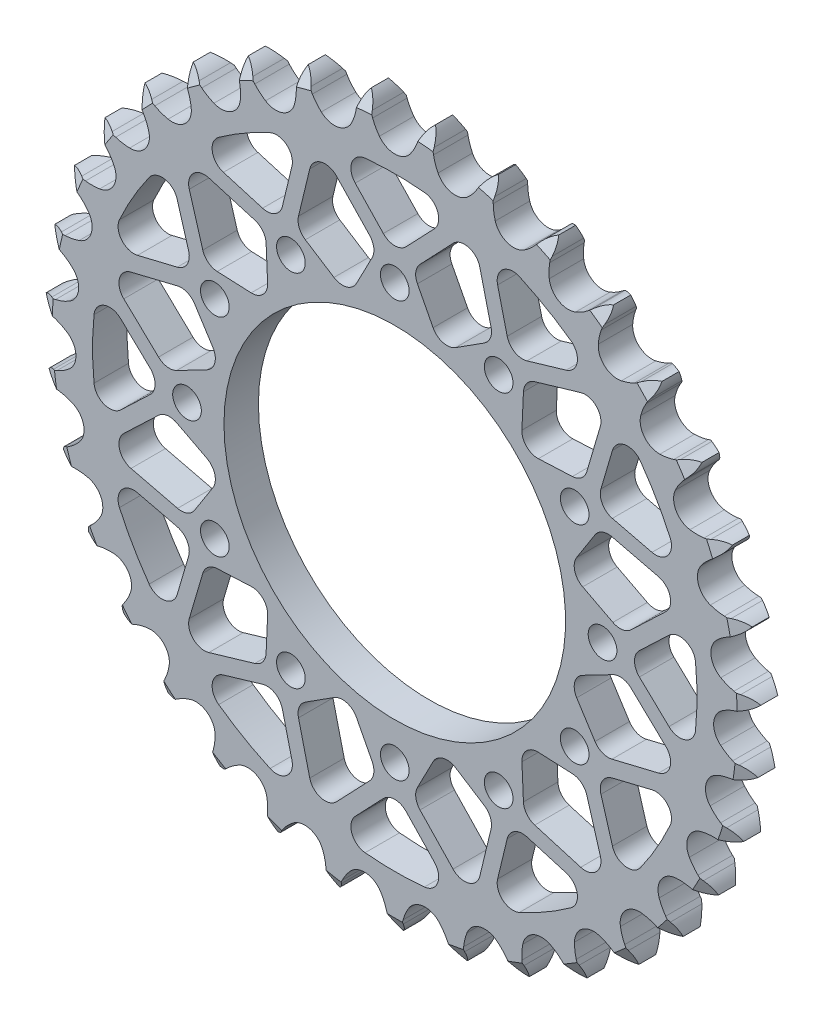
SolidWorks part; units mm, degrees
material "7075-T6 (SN)"
ref_plane "Front Plane" through (0, 0, 0) normal (0, 0, 1) x (1, 0, 0)
ref_plane "Top Plane" through (0, 0, 0) normal (0, 1, 0) x (1, 0, 0)
ref_plane "Right Plane" through (0, 0, 0) normal (1, 0, 0) x (0, 0, -1)
sketch "Work Sketch" plane through (0, 0, 0) normal (0, 0, 1) x (1, 0, 0)
  line L0 (0, 0) -> (0, 160.4542) construction
  line L1 (-112.0919, 70.8395) -> (87.2579, 70.8395) construction
  line L2 (5.0903, 120.8822) -> (5.0903, 112.9699) construction
  line L3 (-12.8497, 74.6356) -> (16.7256, 74.6356) construction
  line L4 (5.0903, 74.6356) -> (-6.074, 66.3097) construction
  line L5 (5.0903, 74.6356) -> (-4.641, 71.0332) construction
  line L6 (-4.641, 71.0332) -> (-6.9559, 77.2865)
  line L7 (-11.5114, 69.8433) -> (-7.1525, 69.8433) construction
  line L8 (-11.0678, 124.7602) -> (-11.0678, 110.2345) construction
  line L9 (0, 0) -> (-3.8324, 42.5811) construction
  circle A0 centre (0, 0) radius 70.8395
  circle A1 centre (0, 70.8395) radius 4.0088
  arc A2 (-4.641, 71.0332) -> (-3.2136, 68.4429) centre (5.0682, 74.6949) ccw
  circle A3 centre (-11.0678, 69.8433) radius 6.4401
  point P23 (-3.2136, 68.4429)
  dimension "D1" = 141.6789
  dimension "D8" = 10.3767
  dimension "D2" = 8.0177
  dimension "D3" = 5.0903
  dimension "D4" = 3.7962
  dimension "D5" = 36.714
  dimension "D6" = 16.4
  dimension "D7" = 10.3767
  dimension "D9" = 0.9961
  dimension "D10" = 11.0678
  dimension "D11" = 5.143
sketch "Teeth Sketch" plane through (0, 0, 0) normal (0, 0, 1) x (1, 0, 0)
  line L0 (5.0282, 72.0792) -> (4.641, 71.0332)
  line L1 (-8.3399, 92.6643) -> (-5.3292, 59.2127) construction
  line L2 (0, 0) -> (-12.1309, 132.2) construction
  line L3 (7.9229, 71.8186) -> (8.1171, 70.7203)
  line L4 (17927.8618, -199194.8588) -> (-17931.6941, 199237.4399) construction
  line L5 (0, 146.3285) -> (0, 56.9858) construction
  line L6 (17.8176, 70.023) -> (17.2498, 69.063)
  line L7 (0, -200000) -> (0, 200160.4542) construction
  line L8 (20.6192, 69.2498) -> (20.6142, 68.1345)
  line L9 (-4.641, 71.0332) -> (-6.9559, 77.2865) construction
  line L10 (43.6371, 57.589) -> (43.2405, 56.5465)
  line L11 (-5.0282, 72.0792) -> (-4.641, 71.0332)
  line L12 (30.0344, 65.7163) -> (29.3043, 64.873)
  line L13 (32.6529, 64.4552) -> (32.4488, 63.3587)
  line L14 (41.2858, 59.2973) -> (40.4169, 58.598)
  line L15 (51.2103, 50.9725) -> (50.2305, 50.4396)
  line L16 (53.2187, 48.8718) -> (52.6424, 47.9169)
  line L17 (59.4888, 41.0094) -> (58.4296, 40.66)
  line L18 (61.0899, 38.5838) -> (60.3523, 37.7472)
  line L19 (65.8553, 29.7283) -> (64.7507, 29.5736)
  line L20 (66.9976, 27.0558) -> (66.1224, 26.3643)
  line L21 (70.1052, 17.4916) -> (68.9907, 17.5366)
  line L22 (70.7519, 14.6581) -> (69.7673, 14.134)
  line L23 (72.1018, 4.6927) -> (71.0133, 4.9361)
  line L24 (72.2322, 1.7893) -> (71.1699, 1.4494)
  line L25 (71.781, -8.2569) -> (70.7534, -7.8232)
  line L26 (71.3909, -11.137) -> (70.2849, -11.2818)
  line L27 (69.1531, -20.9412) -> (68.2195, -20.331)
  line L28 (68.255, -23.7054) -> (67.141, -23.6503)
  line L29 (64.3026, -32.9525) -> (63.493, -32.1853)
  line L30 (62.9254, -35.5118) -> (61.8391, -35.2587)
  line L31 (57.3853, -43.9046) -> (56.7257, -43.0052)
  line L32 (55.5732, -46.1769) -> (54.5496, -45.7339)
  line L33 (48.6237, -53.4456) -> (48.1352, -52.4428)
  line L34 (46.435, -55.3578) -> (45.5069, -54.7392)
  line L35 (38.2992, -61.2688) -> (37.9976, -60.1949)
  line L36 (35.8042, -62.7594) -> (35.0015, -61.985)
  line L37 (26.7437, -67.1227) -> (26.6388, -66.0123)
  line L38 (24.0227, -68.144) -> (23.3712, -67.2387)
  line L39 (14.3287, -70.8193) -> (14.4237, -69.708)
  line L40 (11.4691, -71.3383) -> (10.9896, -70.3312)
  line L41 (1.4532, -72.2397) -> (1.7451, -71.1632)
  line L42 (-1.4532, -72.2397) -> (-1.7451, -71.1632)
  line L43 (-11.4691, -71.3383) -> (-10.9896, -70.3312)
  line L44 (-14.3287, -70.8193) -> (-14.4237, -69.708)
  line L45 (-24.0227, -68.144) -> (-23.3712, -67.2387)
  line L46 (-26.7437, -67.1227) -> (-26.6388, -66.0123)
  line L47 (-35.8042, -62.7594) -> (-35.0015, -61.985)
  line L48 (-38.2992, -61.2688) -> (-37.9976, -60.1949)
  line L49 (-46.435, -55.3578) -> (-45.5069, -54.7392)
  line L50 (-48.6237, -53.4456) -> (-48.1352, -52.4428)
  line L51 (-55.5732, -46.1769) -> (-54.5496, -45.7339)
  line L52 (-57.3853, -43.9046) -> (-56.7257, -43.0052)
  line L53 (-62.9254, -35.5118) -> (-61.8391, -35.2587)
  line L54 (-64.3026, -32.9525) -> (-63.493, -32.1853)
  line L55 (-68.255, -23.7054) -> (-67.141, -23.6503)
  line L56 (-69.1531, -20.9412) -> (-68.2195, -20.331)
  line L57 (-71.3909, -11.137) -> (-70.2849, -11.2818)
  line L58 (-71.781, -8.2569) -> (-70.7534, -7.8232)
  line L59 (-72.2322, 1.7893) -> (-71.1699, 1.4494)
  line L60 (-72.1018, 4.6927) -> (-71.0133, 4.9361)
  line L61 (-70.7519, 14.6581) -> (-69.7673, 14.134)
  line L62 (-70.1052, 17.4916) -> (-68.9907, 17.5366)
  line L63 (-66.9976, 27.0558) -> (-66.1224, 26.3643)
  line L64 (-65.8553, 29.7283) -> (-64.7507, 29.5736)
  line L65 (-61.0899, 38.5838) -> (-60.3523, 37.7472)
  line L66 (-59.4888, 41.0094) -> (-58.4296, 40.66)
  line L67 (-53.2187, 48.8718) -> (-52.6424, 47.9169)
  line L68 (-51.2103, 50.9725) -> (-50.2305, 50.4396)
  line L69 (-43.6371, 57.589) -> (-43.2405, 56.5465)
  line L70 (-41.2858, 59.2973) -> (-40.4169, 58.598)
  line L71 (-32.6529, 64.4552) -> (-32.4488, 63.3587)
  line L72 (-30.0344, 65.7163) -> (-29.3043, 64.873)
  line L73 (-20.6192, 69.2498) -> (-20.6142, 68.1345)
  line L74 (-17.8176, 70.023) -> (-17.2498, 69.063)
  line L75 (-7.9229, 71.8186) -> (-8.1171, 70.7203)
  arc A0 (-6.856, 74.7153) -> (-5.0282, 72.0792) centre (-11.0678, 69.8433) cw
  circle A1 centre (-11.0678, 69.8433) radius 6.4401 construction
  arc A2 (-3.2136, 68.4429) -> (-4.641, 71.0332) centre (5.0682, 74.6949) cw
  arc A3 (-4.641, 71.0332) -> (-3.2136, 68.4429) centre (5.0682, 74.6949) ccw construction
  circle A4 centre (0, 70.8395) radius 4.0088 construction
  arc A5 (-3.2136, 68.4429) -> (3.2136, 68.4429) centre (0, 70.8395) ccw
  arc A6 (3.2136, 68.4429) -> (4.641, 71.0332) centre (-5.0682, 74.6949) ccw
  arc A7 (6.856, 74.7153) -> (5.0282, 72.0792) centre (11.0678, 69.8433) ccw
  arc A8 (6.5951, 74.7388) -> (7.9229, 71.8186) centre (1.5811, 70.6972) cw
  arc A9 (9.059, 67.9168) -> (8.1171, 70.7203) centre (18.324, 72.5896) cw
  arc A10 (9.059, 67.9168) -> (15.3829, 66.7692) centre (12.6489, 69.701) ccw
  arc A11 (15.3829, 66.7692) -> (17.2498, 69.063) centre (8.3506, 74.3995) ccw
  arc A12 (20.0867, 72.2905) -> (17.8176, 70.023) centre (23.3609, 66.7447) ccw
  arc A13 (19.8343, 72.3601) -> (20.6192, 69.2498) centre (14.1792, 69.2787) cw
  arc A14 (21.0404, 65.2078) -> (20.6142, 68.1345) centre (30.9909, 68.1512) cw
  arc A15 (21.0404, 65.2078) -> (27.0578, 62.9494) centre (24.8912, 66.3224) ccw
  arc A16 (27.0578, 62.9494) -> (29.3043, 64.873) centre (21.5009, 71.7128) ccw
  arc A17 (32.6719, 67.5421) -> (30.0344, 65.7163) centre (34.9032, 61.5008) ccw
  arc A18 (32.4359, 67.6557) -> (32.6529, 64.4552) centre (26.3215, 65.6336) cw
  arc A19 (32.3456, 60.403) -> (32.4488, 63.3587) centre (42.6617, 61.5223) cw
  arc A20 (32.3456, 60.403) -> (37.863, 57.1065) centre (36.3335, 60.812) ccw
  arc A21 (37.863, 57.1065) -> (40.4169, 58.598) centre (33.9602, 66.7212) ccw
  arc A22 (44.207, 60.6229) -> (41.2858, 59.2973) centre (45.3237, 54.2803) ccw
  arc A23 (43.9951, 60.7768) -> (43.6371, 57.589) centre (37.6178, 59.8789) cw
  arc A24 (42.6112, 53.6567) -> (43.2405, 56.5465) centre (52.9614, 52.9161) cw
  arc A25 (42.6112, 53.6567) -> (47.4513, 49.428) centre (46.608, 53.3472) ccw
  arc A26 (47.4513, 49.428) -> (50.2305, 50.4396) centre (45.328, 59.5852) ccw
  arc A27 (54.3212, 51.7552) -> (51.2103, 50.9725) centre (54.2875, 45.3151) ccw
  arc A28 (54.1402, 51.9445) -> (53.2187, 48.8718) centre (47.7051, 52.1997) cw
  arc A29 (51.5072, 45.1859) -> (52.6424, 47.9169) centre (61.5588, 42.6091) cw
  arc A30 (51.5072, 45.1859) -> (55.5144, 40.161) centre (55.3845, 44.1677) ccw
  arc A31 (55.5144, 40.161) -> (58.4296, 40.66) centre (55.2389, 50.534) ccw
  arc A32 (62.6894, 41.224) -> (59.4888, 41.0094) centre (61.5064, 34.8935) ccw
  arc A33 (62.5452, 41.4426) -> (61.0899, 38.5838) centre (56.2591, 42.8428) cw
  arc A34 (58.7477, 35.2628) -> (60.3523, 37.7472) centre (68.1777, 30.9326) cw
  arc A35 (58.7477, 35.2628) -> (61.7933, 29.6031) centre (62.3809, 33.5686) ccw
  arc A36 (61.7933, 29.6031) -> (64.7507, 29.5736) centre (63.3744, 39.8586) ccw
  arc A37 (69.0428, 29.3679) -> (65.8553, 29.7283) centre (66.7484, 23.3503) ccw
  arc A38 (68.9399, 29.6087) -> (66.9976, 27.0558) centre (63.0048, 32.1088) cw
  arc A39 (64.1, 24.2063) -> (66.1224, 26.3643) centre (72.6052, 18.2619) cw
  arc A40 (64.1, 24.2063) -> (66.0861, 18.0937) centre (67.3723, 21.8906) ccw
  arc A41 (66.0861, 18.0937) -> (68.9907, 17.5366) centre (69.4729, 27.9021) ccw
  arc A42 (73.1771, 16.5679) -> (70.1052, 17.4916) centre (69.8451, 11.0567) ccw
  arc A43 (73.1188, 16.8232) -> (70.7519, 14.6581) centre (67.7256, 20.3429) cw
  arc A44 (67.3921, 12.3718) -> (69.7673, 14.134) centre (74.6992, 5.0042) cw
  arc A45 (67.3921, 12.3718) -> (68.2548, 6.0028) centre (70.1983, 9.509) ccw
  arc A46 (68.2548, 6.0028) -> (71.0133, 4.9361) centre (73.3386, 15.0489) ccw
  arc A47 (74.9595, 3.2354) -> (72.1018, 4.6927) centre (70.6969, -1.5923) ccw
  arc A48 (74.9477, 3.497) -> (72.2322, 1.7893) centre (70.2696, 7.9231) cw
  arc A49 (68.5181, 0.1397) -> (71.1699, 1.4494) centre (74.3923, -8.4143) cw
  arc A50 (68.5181, 0.1397) -> (68.2298, -6.281) centre (70.7681, -3.1782) ccw
  arc A51 (68.2298, -6.281) -> (70.7534, -7.8232) centre (74.8471, 1.7119) ccw
  arc A52 (74.3325, -10.2012) -> (71.781, -8.2569) centre (69.2765, -14.1901) ccw
  arc A53 (74.3677, -9.9416) -> (71.3909, -11.137) centre (70.555, -4.7513) cw
  arc A54 (67.442, -12.097) -> (70.2849, -11.2818) centre (71.6944, -21.5623) cw
  arc A55 (67.442, -12.097) -> (66.0118, -18.363) centre (69.0634, -15.7633) ccw
  arc A56 (66.0118, -18.363) -> (68.2195, -20.331) centre (73.9499, -11.6801) ccw
  arc A57 (71.3165, -23.3098) -> (69.1531, -20.9412) centre (65.6294, -26.3319) ccw
  arc A58 (71.3974, -23.0607) -> (68.255, -23.7054) centre (68.5728, -17.2731) cw
  arc A59 (64.1981, -23.9448) -> (67.141, -23.6503) centre (66.6921, -34.0173) cw
  arc A60 (64.1981, -23.9448) -> (61.6721, -29.8547) centre (65.1388, -27.8417) ccw
  arc A61 (61.6721, -29.8547) -> (63.493, -32.1853) centre (70.676, -24.6966) ccw
  arc A62 (66.0083, -35.6693) -> (64.3026, -32.9525) centre (59.873, -37.6273) ccw
  arc A63 (66.1324, -35.4386) -> (62.9254, -35.5118) centre (64.3866, -29.2396) cw
  arc A64 (58.8909, -35.023) -> (61.8391, -35.2587) centre (59.5463, -45.379) cw
  arc A65 (58.8909, -35.023) -> (55.3502, -40.3869) centre (59.1207, -39.0252) ccw
  arc A66 (55.3502, -40.3869) -> (56.7257, -43.0052) centre (65.1304, -36.9194) ccw
  arc A67 (58.5785, -46.8823) -> (57.3853, -43.9046) centre (52.1922, -47.7133) ccw
  arc A68 (58.7418, -46.6775) -> (55.5732, -46.1769) centre (58.1309, -40.2664) cw
  arc A69 (51.6909, -44.9755) -> (54.5496, -45.7339) centre (50.4867, -55.2821) cw
  arc A70 (51.6909, -44.9755) -> (47.2494, -49.6211) centre (51.2024, -48.9545) ccw
  arc A71 (47.2494, -49.6211) -> (48.1352, -52.4428) centre (57.4915, -47.9556) ccw
  arc A72 (49.266, -56.5885) -> (48.6237, -53.4456) centre (42.8339, -56.2658) ccw
  arc A73 (49.4632, -56.4161) -> (46.435, -55.3578) centre (50.0069, -49.999) cw
  arc A74 (42.8296, -53.4825) -> (45.5069, -54.7392) centre (39.8043, -63.4085) cw
  arc A75 (42.8296, -53.4825) -> (37.6299, -57.2603) centre (41.6384, -57.3103) ccw
  arc A76 (37.6299, -57.2603) -> (37.9976, -60.1949) centre (48.0048, -57.4505) ccw
  arc A77 (38.37, -64.4758) -> (38.2992, -61.2688) centre (32.0989, -63.0099) ccw
  arc A78 (38.5948, -64.3415) -> (35.8042, -62.7594) centre (40.2756, -58.1246) cw
  arc A79 (32.5916, -60.2706) -> (35.0015, -61.985) centre (27.8426, -69.4968) cw
  arc A80 (32.5916, -60.2706) -> (26.8009, -63.0592) centre (30.7361, -63.8241) ccw
  arc A81 (26.8009, -63.0592) -> (26.6388, -66.0123) centre (36.9752, -65.0988) ccw
  arc A82 (26.2407, -70.2909) -> (26.7437, -67.1227) centre (20.3322, -67.7288) ccw
  arc A83 (26.4859, -70.1989) -> (24.0227, -68.144) centre (29.2498, -64.382) cw
  arc A84 (21.3061, -65.1215) -> (23.3712, -67.2387) centre (14.9861, -73.3515) cw
  arc A85 (21.3061, -65.1215) -> (15.1105, -66.8313) centre (18.8459, -68.2866) ccw
  arc A86 (15.1105, -66.8313) -> (14.4237, -69.708) centre (24.7571, -70.6548) ccw
  arc A87 (13.2681, -73.8468) -> (14.3287, -70.8193) centre (7.912, -70.2708) ccw
  arc A88 (13.5258, -73.8) -> (11.4691, -71.3383) centre (17.2839, -68.5701) cw
  arc A89 (9.3358, -67.8793) -> (10.9896, -70.3312) centre (1.6478, -74.8485) cw
  arc A90 (9.3358, -67.8793) -> (2.9345, -68.4554) centre (6.35, -70.5543) ccw
  arc A91 (2.9345, -68.4554) -> (1.7451, -71.1632) centre (11.7434, -73.9399) ccw
  arc A92 (-0.131, -75.0291) -> (1.4532, -72.2397) centre (-4.7625, -70.5543) ccw
  arc A93 (0.131, -75.0291) -> (-1.4532, -72.2397) centre (4.7625, -70.5543) cw
  arc A94 (-2.9345, -68.4554) -> (-1.7451, -71.1632) centre (-11.7434, -73.9399) cw
  arc A95 (-2.9345, -68.4554) -> (-9.3358, -67.8793) centre (-6.35, -70.5543) ccw
  arc A96 (-9.3358, -67.8793) -> (-10.9896, -70.3312) centre (-1.6478, -74.8485) ccw
  arc A97 (-13.5258, -73.8) -> (-11.4691, -71.3383) centre (-17.2839, -68.5701) ccw
  arc A98 (-13.2681, -73.8468) -> (-14.3287, -70.8193) centre (-7.912, -70.2708) cw
  arc A99 (-15.1105, -66.8313) -> (-14.4237, -69.708) centre (-24.7571, -70.6548) cw
  arc A100 (-15.1105, -66.8313) -> (-21.3061, -65.1215) centre (-18.8459, -68.2866) ccw
  arc A101 (-21.3061, -65.1215) -> (-23.3712, -67.2387) centre (-14.9861, -73.3515) ccw
  arc A102 (-26.4859, -70.1989) -> (-24.0227, -68.144) centre (-29.2498, -64.382) ccw
  arc A103 (-26.2407, -70.2909) -> (-26.7437, -67.1227) centre (-20.3322, -67.7288) cw
  arc A104 (-26.8009, -63.0592) -> (-26.6388, -66.0123) centre (-36.9752, -65.0988) cw
  arc A105 (-26.8009, -63.0592) -> (-32.5916, -60.2706) centre (-30.7361, -63.8241) ccw
  arc A106 (-32.5916, -60.2706) -> (-35.0015, -61.985) centre (-27.8426, -69.4968) ccw
  arc A107 (-38.5948, -64.3415) -> (-35.8042, -62.7594) centre (-40.2756, -58.1246) ccw
  arc A108 (-38.37, -64.4758) -> (-38.2992, -61.2688) centre (-32.0989, -63.0099) cw
  arc A109 (-37.6299, -57.2603) -> (-37.9976, -60.1949) centre (-48.0048, -57.4505) cw
  arc A110 (-37.6299, -57.2603) -> (-42.8296, -53.4825) centre (-41.6384, -57.3103) ccw
  arc A111 (-42.8296, -53.4825) -> (-45.5069, -54.7392) centre (-39.8043, -63.4085) ccw
  arc A112 (-49.4632, -56.4161) -> (-46.435, -55.3578) centre (-50.0069, -49.999) ccw
  arc A113 (-49.266, -56.5885) -> (-48.6237, -53.4456) centre (-42.8339, -56.2658) cw
  arc A114 (-47.2494, -49.6211) -> (-48.1352, -52.4428) centre (-57.4915, -47.9556) cw
  arc A115 (-47.2494, -49.6211) -> (-51.6909, -44.9755) centre (-51.2024, -48.9545) ccw
  arc A116 (-51.6909, -44.9755) -> (-54.5496, -45.7339) centre (-50.4867, -55.2821) ccw
  arc A117 (-58.7418, -46.6775) -> (-55.5732, -46.1769) centre (-58.1309, -40.2664) ccw
  arc A118 (-58.5785, -46.8823) -> (-57.3853, -43.9046) centre (-52.1922, -47.7133) cw
  arc A119 (-55.3502, -40.3869) -> (-56.7257, -43.0052) centre (-65.1304, -36.9194) cw
  arc A120 (-55.3502, -40.3869) -> (-58.8909, -35.023) centre (-59.1207, -39.0252) ccw
  arc A121 (-58.8909, -35.023) -> (-61.8391, -35.2587) centre (-59.5463, -45.379) ccw
  arc A122 (-66.1324, -35.4386) -> (-62.9254, -35.5118) centre (-64.3866, -29.2396) ccw
  arc A123 (-66.0083, -35.6693) -> (-64.3026, -32.9525) centre (-59.873, -37.6273) cw
  arc A124 (-61.6721, -29.8547) -> (-63.493, -32.1853) centre (-70.676, -24.6966) cw
  arc A125 (-61.6721, -29.8547) -> (-64.1981, -23.9448) centre (-65.1388, -27.8417) ccw
  arc A126 (-64.1981, -23.9448) -> (-67.141, -23.6503) centre (-66.6921, -34.0173) ccw
  arc A127 (-71.3974, -23.0607) -> (-68.255, -23.7054) centre (-68.5728, -17.2731) ccw
  arc A128 (-71.3165, -23.3098) -> (-69.1531, -20.9412) centre (-65.6294, -26.3319) cw
  arc A129 (-66.0118, -18.363) -> (-68.2195, -20.331) centre (-73.9499, -11.6801) cw
  arc A130 (-66.0118, -18.363) -> (-67.442, -12.097) centre (-69.0634, -15.7633) ccw
  arc A131 (-67.442, -12.097) -> (-70.2849, -11.2818) centre (-71.6944, -21.5623) ccw
  arc A132 (-74.3677, -9.9416) -> (-71.3909, -11.137) centre (-70.555, -4.7513) ccw
  arc A133 (-74.3325, -10.2012) -> (-71.781, -8.2569) centre (-69.2765, -14.1901) cw
  arc A134 (-68.2298, -6.281) -> (-70.7534, -7.8232) centre (-74.8471, 1.7119) cw
  arc A135 (-68.2298, -6.281) -> (-68.5181, 0.1397) centre (-70.7681, -3.1782) ccw
  arc A136 (-68.5181, 0.1397) -> (-71.1699, 1.4494) centre (-74.3923, -8.4143) ccw
  arc A137 (-74.9477, 3.497) -> (-72.2322, 1.7893) centre (-70.2696, 7.9231) ccw
  arc A138 (-74.9595, 3.2354) -> (-72.1018, 4.6927) centre (-70.6969, -1.5923) cw
  arc A139 (-68.2548, 6.0028) -> (-71.0133, 4.9361) centre (-73.3386, 15.0489) cw
  arc A140 (-68.2548, 6.0028) -> (-67.3921, 12.3718) centre (-70.1983, 9.509) ccw
  arc A141 (-67.3921, 12.3718) -> (-69.7673, 14.134) centre (-74.6992, 5.0042) ccw
  arc A142 (-73.1188, 16.8232) -> (-70.7519, 14.6581) centre (-67.7256, 20.3429) ccw
  arc A143 (-73.1771, 16.5679) -> (-70.1052, 17.4916) centre (-69.8451, 11.0567) cw
  arc A144 (-66.0861, 18.0937) -> (-68.9907, 17.5366) centre (-69.4729, 27.9021) cw
  arc A145 (-66.0861, 18.0937) -> (-64.1, 24.2063) centre (-67.3723, 21.8906) ccw
  arc A146 (-64.1, 24.2063) -> (-66.1224, 26.3643) centre (-72.6052, 18.2619) ccw
  arc A147 (-68.9399, 29.6087) -> (-66.9976, 27.0558) centre (-63.0048, 32.1088) ccw
  arc A148 (-69.0428, 29.3679) -> (-65.8553, 29.7283) centre (-66.7484, 23.3503) cw
  arc A149 (-61.7933, 29.6031) -> (-64.7507, 29.5736) centre (-63.3744, 39.8586) cw
  arc A150 (-61.7933, 29.6031) -> (-58.7477, 35.2628) centre (-62.3809, 33.5686) ccw
  arc A151 (-58.7477, 35.2628) -> (-60.3523, 37.7472) centre (-68.1777, 30.9326) ccw
  arc A152 (-62.5452, 41.4426) -> (-61.0899, 38.5838) centre (-56.2591, 42.8428) ccw
  arc A153 (-62.6894, 41.224) -> (-59.4888, 41.0094) centre (-61.5064, 34.8935) cw
  arc A154 (-55.5144, 40.161) -> (-58.4296, 40.66) centre (-55.2389, 50.534) cw
  arc A155 (-55.5144, 40.161) -> (-51.5072, 45.1859) centre (-55.3845, 44.1677) ccw
  arc A156 (-51.5072, 45.1859) -> (-52.6424, 47.9169) centre (-61.5588, 42.6091) ccw
  arc A157 (-54.1402, 51.9445) -> (-53.2187, 48.8718) centre (-47.7051, 52.1997) ccw
  arc A158 (-54.3212, 51.7552) -> (-51.2103, 50.9725) centre (-54.2875, 45.3151) cw
  arc A159 (-47.4513, 49.428) -> (-50.2305, 50.4396) centre (-45.328, 59.5852) cw
  arc A160 (-47.4513, 49.428) -> (-42.6112, 53.6567) centre (-46.608, 53.3472) ccw
  arc A161 (-42.6112, 53.6567) -> (-43.2405, 56.5465) centre (-52.9614, 52.9161) ccw
  arc A162 (-43.9951, 60.7768) -> (-43.6371, 57.589) centre (-37.6178, 59.8789) ccw
  arc A163 (-44.207, 60.6229) -> (-41.2858, 59.2973) centre (-45.3237, 54.2803) cw
  arc A164 (-37.863, 57.1065) -> (-40.4169, 58.598) centre (-33.9602, 66.7212) cw
  arc A165 (-37.863, 57.1065) -> (-32.3456, 60.403) centre (-36.3335, 60.812) ccw
  arc A166 (-32.3456, 60.403) -> (-32.4488, 63.3587) centre (-42.6617, 61.5223) ccw
  arc A167 (-32.4359, 67.6557) -> (-32.6529, 64.4552) centre (-26.3215, 65.6336) ccw
  arc A168 (-32.6719, 67.5421) -> (-30.0344, 65.7163) centre (-34.9032, 61.5008) cw
  arc A169 (-27.0578, 62.9494) -> (-29.3043, 64.873) centre (-21.5009, 71.7128) cw
  arc A170 (-27.0578, 62.9494) -> (-21.0404, 65.2078) centre (-24.8912, 66.3224) ccw
  arc A171 (-21.0404, 65.2078) -> (-20.6142, 68.1345) centre (-30.9909, 68.1512) ccw
  arc A172 (-19.8343, 72.3601) -> (-20.6192, 69.2498) centre (-14.1792, 69.2787) ccw
  arc A173 (-20.0867, 72.2905) -> (-17.8176, 70.023) centre (-23.3609, 66.7447) cw
  arc A174 (-15.3829, 66.7692) -> (-17.2498, 69.063) centre (-8.3506, 74.3995) cw
  arc A175 (-15.3829, 66.7692) -> (-9.059, 67.9168) centre (-12.6489, 69.701) ccw
  arc A176 (-9.059, 67.9168) -> (-8.1171, 70.7203) centre (-18.324, 72.5896) ccw
  arc A177 (-6.5951, 74.7388) -> (-7.9229, 71.8186) centre (-1.5811, 70.6972) ccw
  point P77 (0, 0)
  dimension "D1" = 5.143
  dimension "D2" = 5.243
  dimension "D3" = 35
extrude "Extrusion" add sketch "Teeth Sketch" along normal blind 7.2136 contours A0 region at (0, 0, 0)
sketch "Sketch1" plane through (0, 0, 0) normal (0, 0, -1) x (-1, 0, 0)
  circle A0 centre (0, 0) radius 78.9443
  circle A1 centre (0, 0) radius 35.7643
  dimension "D1" = 43.18
extrude "Cut-Extrude" cut sketch "Sketch1" against normal through all both and the other way through all contours A1
ref_axis "Axis2" through (0, 0, -0.3607) along (0, 0, 1)
ref_axis "Axis1" [suppressed] through (0, 0, 7.2136) along (0, 0, -1)
ref_plane "Sprocket Center Plane" through (0, 0, 3.6068) normal (0, 0, 1) x (1, 0, 0)
sketch "Pitch Circle" plane through (0, 0, 3.6068) normal (0, 0, -1) x (-1, 0, 0)
  circle A0 centre (0, 0) radius 82.9531 construction
  dimension "D1" = 165.9063
sketch "Chain Pitch Circle" plane through (0, 0, 0) normal (0, 0, -1) x (-1, 0, 0)
  circle A0 centre (0, 0) radius 82.9531 construction
  dimension "D1" = 165.9063
ref_plane "Center Plane" through (0, 0, 3.6068) normal (0, 0, 1) x (1, 0, 0)
hole_wizard "Ø6.0mm Dowel Hole1" positions "Sketch7" profile "Sketch8" hole size "Ø6.0" standard "ANSI Metric" end condition through all
sketch "Sketch7" plane through (0, 0, 7.2136) normal (0, 0, 1) x (1, 0, 0)
  point P0 (-43.5, 0)
  dimension "D1" = 43.5
sketch "Sketch8" plane through (-43.5, 0, 7.2136) normal (1, 0, 0) x (0, -1, 0)
  line L0 (0, 0) -> (0, 7.2136)
  line L1 (0, 7.2136) -> (3, 7.2136)
  line L2 (3, 7.2136) -> (3, 0)
  line L5 (3, 0) -> (0, 0)
  line L11 (0, -6.35) -> (0, 107.95) construction
  dimension "Thru Hole Dia." = 6
  dimension "Thru Hole Depth" = 7.2136
pattern_circular "CirPattern1" count 12 over 360 about axis through (0, 0, 7.2136) along (0, 0, -1) of "Ø6.0mm Dowel Hole1" reverse direction yes
ref_plane "Plane1" through (0, 0, 3.6068) normal (0, 0, -1) x (-1, 0, 0)
sketch "Sketch9" plane through (0, 0, 0) normal (0, 0, 1) x (1, 0, 0)
  line L0 (-43.5, 0) -> (-63.2746, 0) construction
  line L1 (-61.9966, 12.6533) -> (-48.707, 0)
  line L2 (-61.9966, -12.6533) -> (-48.707, 0)
  line L11 (-43.5, 0) -> (-37.6721, 21.75) construction
  line L13 (-61.1186, 16.3767) -> (-36.1404, 9.6838) construction
  line L18 (-43.1887, 20.7127) -> (-36.1404, 9.6838)
  line L19 (-47.7589, 3.6566) -> (-36.1404, 9.6838)
  line L20 (-43.1887, 20.7127) -> (-61.1186, 16.3767)
  line L21 (-47.7589, 3.6566) -> (-61.1186, 16.3767)
  circle A0 centre (0, 0) radius 66.8306 construction
  arc A1 (-15.3829, 66.7692) -> (-9.059, 67.9168) centre (-12.6489, 69.701) ccw construction
  circle A2 centre (-43.5, 0) radius 3 construction
  circle A3 centre (-43.5, 0) radius 5.207
  circle A4 centre (-37.6721, 21.75) radius 3 construction
  circle A6 centre (-37.6721, 21.75) radius 5.207
  circle A196 centre (0, 0) radius 63.2746
  circle A197 centre (0, 0) radius 35.7643 construction
  circle A198 centre (0, 0) radius 35.7643
  circle A199 centre (0, 0) radius 37.4153 construction
  point P17 (-40.5861, 10.875)
  dimension "D1" = 3.556
  dimension "D2" = 1.651
  dimension "D3" = 10.414
  dimension "D4" = 3.302
extrude "Cut-Extrude2" cut sketch "Sketch9" along normal through all contours L1 A196 L2 | L21 L19 L18 L20 region at (-58.1293, 0, 0) region at (-47.5776, 12.7484, 0)
fillet "Fillet2" radius 3.302 7 edges at (-61.1186, 16.3767, 3.6068) (-36.1404, 9.6838, 3.6068) (-47.7589, 3.6566, 3.6068) (-43.1887, 20.7127, 3.6068) (-61.9966, -12.6533, 3.6068) (-48.707, 0, 3.6068) (-61.9966, 12.6533, 3.6068)
pattern_circular "CirPattern3" count 12 over 360 about axis through (0, 0, 7.2136) along (0, 0, -1) of "Cut-Extrude2", "Fillet2"
sketch "Sketch14" plane through (0, 0, 7.2136) normal (0, 0, 1) x (1, 0, 0)
  line L0 (-45.6677, -4.7414) -> (-39.3483, -8.0197) construction
  line L1 (-38.2956, 5.9905) -> (-37.9766, 6.1559)
  line L2 (-43.5, 0) -> (-38.293, 0) construction
  line L3 (-38.2956, -5.9905) -> (-37.9766, -6.1559)
  line L4 (-30.1697, 24.3357) -> (-29.8108, 24.3195)
  line L5 (-36.1602, 13.9599) -> (-35.9667, 13.6571)
  line L6 (-13.9599, 36.1602) -> (-13.6571, 35.9667)
  line L7 (-24.3357, 30.1697) -> (-24.3195, 29.8108)
  line L8 (5.9905, 38.2956) -> (6.1559, 37.9766)
  line L9 (-5.9905, 38.2956) -> (-6.1559, 37.9766)
  line L10 (24.3357, 30.1697) -> (24.3195, 29.8108)
  line L11 (13.9599, 36.1602) -> (13.6571, 35.9667)
  line L12 (36.1602, 13.9599) -> (35.9667, 13.6571)
  line L13 (30.1697, 24.3357) -> (29.8108, 24.3195)
  line L14 (38.2956, -5.9905) -> (37.9766, -6.1559)
  line L15 (38.2956, 5.9905) -> (37.9766, 6.1559)
  line L16 (30.1697, -24.3357) -> (29.8108, -24.3195)
  line L17 (36.1602, -13.9599) -> (35.9667, -13.6571)
  line L18 (13.9599, -36.1602) -> (13.6571, -35.9667)
  line L19 (24.3357, -30.1697) -> (24.3195, -29.8108)
  line L20 (-5.9905, -38.2956) -> (-6.1559, -37.9766)
  line L21 (5.9905, -38.2956) -> (6.1559, -37.9766)
  line L22 (-24.3357, -30.1697) -> (-24.3195, -29.8108)
  line L23 (-13.9599, -36.1602) -> (-13.6571, -35.9667)
  line L24 (-36.1602, -13.9599) -> (-35.9667, -13.6571)
  line L25 (-30.1697, -24.3357) -> (-29.8108, -24.3195)
  arc A0 (-39.0014, -2.6222) -> (-39.0014, 2.6222) centre (-43.5, 0) ccw
  circle A1 centre (0, 0) radius 35.7643 construction
  arc A2 (-37.9766, -6.1559) -> (-39.0014, -2.6222) centre (-36.807, -3.9013) cw
  arc A3 (-38.2956, 5.9905) -> (-36.1602, 13.9599) centre (-40.8688, 10.9508) ccw
  arc A4 (-38.2956, 5.9905) -> (-36.1602, 13.9599) centre (-40.8688, 10.9508) ccw
  arc A5 (-37.9766, 6.1559) -> (-39.0014, 2.6222) centre (-36.807, 3.9013) ccw
  circle A6 centre (0, 0) radius 35.7643
  arc A7 (-30.1697, 24.3357) -> (-24.3357, 30.1697) centre (-29.918, 29.918) ccw
  arc A8 (-29.8108, 24.3195) -> (-32.4651, 21.7716) centre (-29.9252, 21.7821) ccw
  arc A9 (-35.0873, 17.2299) -> (-32.4651, 21.7716) centre (-37.6721, 21.75) ccw
  arc A10 (-35.9667, 13.6571) -> (-35.0873, 17.2299) centre (-33.8264, 15.0249) cw
  arc A11 (-13.9599, 36.1602) -> (-5.9905, 38.2956) centre (-10.9508, 40.8688) ccw
  arc A12 (-13.6571, 35.9667) -> (-17.2299, 35.0873) centre (-15.0249, 33.8264) ccw
  arc A13 (-21.7716, 32.4651) -> (-17.2299, 35.0873) centre (-21.75, 37.6721) ccw
  arc A14 (-24.3195, 29.8108) -> (-21.7716, 32.4651) centre (-21.7821, 29.9252) cw
  arc A15 (5.9905, 38.2956) -> (13.9599, 36.1602) centre (10.9508, 40.8688) ccw
  arc A16 (6.1559, 37.9766) -> (2.6222, 39.0014) centre (3.9013, 36.807) ccw
  arc A17 (-2.6222, 39.0014) -> (2.6222, 39.0014) centre (0, 43.5) ccw
  arc A18 (-6.1559, 37.9766) -> (-2.6222, 39.0014) centre (-3.9013, 36.807) cw
  arc A19 (24.3357, 30.1697) -> (30.1697, 24.3357) centre (29.918, 29.918) ccw
  arc A20 (24.3195, 29.8108) -> (21.7716, 32.4651) centre (21.7821, 29.9252) ccw
  arc A21 (17.2299, 35.0873) -> (21.7716, 32.4651) centre (21.75, 37.6721) ccw
  arc A22 (13.6571, 35.9667) -> (17.2299, 35.0873) centre (15.0249, 33.8264) cw
  arc A23 (36.1602, 13.9599) -> (38.2956, 5.9905) centre (40.8688, 10.9508) ccw
  arc A24 (35.9667, 13.6571) -> (35.0873, 17.2299) centre (33.8264, 15.0249) ccw
  arc A25 (32.4651, 21.7716) -> (35.0873, 17.2299) centre (37.6721, 21.75) ccw
  arc A26 (29.8108, 24.3195) -> (32.4651, 21.7716) centre (29.9252, 21.7821) cw
  arc A27 (38.2956, -5.9905) -> (36.1602, -13.9599) centre (40.8688, -10.9508) ccw
  arc A28 (37.9766, -6.1559) -> (39.0014, -2.6222) centre (36.807, -3.9013) ccw
  arc A29 (39.0014, 2.6222) -> (39.0014, -2.6222) centre (43.5, 0) ccw
  arc A30 (37.9766, 6.1559) -> (39.0014, 2.6222) centre (36.807, 3.9013) cw
  arc A31 (30.1697, -24.3357) -> (24.3357, -30.1697) centre (29.918, -29.918) ccw
  arc A32 (29.8108, -24.3195) -> (32.4651, -21.7716) centre (29.9252, -21.7821) ccw
  arc A33 (35.0873, -17.2299) -> (32.4651, -21.7716) centre (37.6721, -21.75) ccw
  arc A34 (35.9667, -13.6571) -> (35.0873, -17.2299) centre (33.8264, -15.0249) cw
  arc A35 (13.9599, -36.1602) -> (5.9905, -38.2956) centre (10.9508, -40.8688) ccw
  arc A36 (13.6571, -35.9667) -> (17.2299, -35.0873) centre (15.0249, -33.8264) ccw
  arc A37 (21.7716, -32.4651) -> (17.2299, -35.0873) centre (21.75, -37.6721) ccw
  arc A38 (24.3195, -29.8108) -> (21.7716, -32.4651) centre (21.7821, -29.9252) cw
  arc A39 (-5.9905, -38.2956) -> (-13.9599, -36.1602) centre (-10.9508, -40.8688) ccw
  arc A40 (-6.1559, -37.9766) -> (-2.6222, -39.0014) centre (-3.9013, -36.807) ccw
  arc A41 (2.6222, -39.0014) -> (-2.6222, -39.0014) centre (0, -43.5) ccw
  arc A42 (6.1559, -37.9766) -> (2.6222, -39.0014) centre (3.9013, -36.807) cw
  arc A43 (-24.3357, -30.1697) -> (-30.1697, -24.3357) centre (-29.918, -29.918) ccw
  arc A44 (-24.3195, -29.8108) -> (-21.7716, -32.4651) centre (-21.7821, -29.9252) ccw
  arc A45 (-17.2299, -35.0873) -> (-21.7716, -32.4651) centre (-21.75, -37.6721) ccw
  arc A46 (-13.6571, -35.9667) -> (-17.2299, -35.0873) centre (-15.0249, -33.8264) cw
  arc A47 (-36.1602, -13.9599) -> (-38.2956, -5.9905) centre (-40.8688, -10.9508) ccw
  arc A48 (-35.9667, -13.6571) -> (-35.0873, -17.2299) centre (-33.8264, -15.0249) ccw
  arc A49 (-32.4651, -21.7716) -> (-35.0873, -17.2299) centre (-37.6721, -21.75) ccw
  arc A50 (-29.8108, -24.3195) -> (-32.4651, -21.7716) centre (-29.9252, -21.7821) cw
  point P10 (-41.0188, -4.5778)
  point P16 (-41.0188, 4.5778)
  point P144 (0, 0)
  dimension "D2" = 2.54
  dimension "D1" = 2.286
  dimension "D3" = 12
extrude "Cut-Extrude7" [suppressed] cut sketch "Sketch14" against normal through all
sketch "Sketch19" plane through (0, 0, 0) normal (0, 0, 1) x (1, 0, 0)
  circle A0 centre (0, 0) radius 72.898 construction
  dimension "D1" = 145.796
sketch "Sketch15" plane through (0, 0, 0) normal (0, 0, -1) x (-1, 0, 0)
  line L9 (-30.8009, 49.3753) -> (-28.037, 48.5615)
  line L10 (-28.037, 48.5615) -> (-27.3598, 51.362)
  line L11 (-48.5615, 28.037) -> (-49.3753, 30.8009)
  line L12 (-51.362, 27.3598) -> (-48.5615, 28.037)
  line L13 (-48.5615, 28.037) -> (-49.3753, 30.8009)
  line L14 (-51.362, 27.3598) -> (-48.5615, 28.037)
  line L15 (-46.8809, 9.8349) -> (-43.4148, 11.633)
  line L16 (-50.8663, 13.6296) -> (-46.8809, 9.8349)
  line L17 (-45.5175, 14.9231) -> (-50.8663, 13.6296)
  line L18 (-43.4148, 11.633) -> (-45.5175, 14.9231)
  line L19 (-46.8809, 9.8349) -> (-43.4148, 11.633)
  line L20 (-50.8663, 13.6296) -> (-46.8809, 9.8349)
  line L21 (-45.5175, 14.9231) -> (-50.8663, 13.6296)
  line L22 (-43.4148, 11.633) -> (-45.5175, 14.9231)
  line L23 (-37.2367, 37.2367) -> (-35.6825, 31.9577)
  line L24 (-35.6825, 31.9577) -> (-31.7819, 31.7819)
  line L25 (-31.7819, 31.7819) -> (-31.9577, 35.6825)
  line L26 (-31.9577, 35.6825) -> (-37.2367, 37.2367)
  line L27 (-1.9867, 58.1607) -> (0, 56.074)
  line L28 (0, 56.074) -> (1.9867, 58.1607)
  line L29 (-13.6296, 50.8663) -> (-14.9231, 45.5175)
  line L30 (-14.9231, 45.5175) -> (-11.633, 43.4148)
  line L31 (-11.633, 43.4148) -> (-9.8349, 46.8809)
  line L32 (-9.8349, 46.8809) -> (-13.6296, 50.8663)
  line L33 (27.3598, 51.362) -> (28.037, 48.5615)
  line L34 (28.037, 48.5615) -> (30.8009, 49.3753)
  line L35 (13.6296, 50.8663) -> (9.8349, 46.8809)
  line L36 (9.8349, 46.8809) -> (11.633, 43.4148)
  line L37 (11.633, 43.4148) -> (14.9231, 45.5175)
  line L38 (14.9231, 45.5175) -> (13.6296, 50.8663)
  line L39 (49.3753, 30.8009) -> (48.5615, 28.037)
  line L40 (48.5615, 28.037) -> (51.362, 27.3598)
  line L41 (37.2367, 37.2367) -> (31.9577, 35.6825)
  line L42 (31.9577, 35.6825) -> (31.7819, 31.7819)
  line L43 (31.7819, 31.7819) -> (35.6825, 31.9577)
  line L44 (35.6825, 31.9577) -> (37.2367, 37.2367)
  line L45 (58.1607, 1.9867) -> (56.074, 0)
  line L46 (56.074, 0) -> (58.1607, -1.9867)
  line L47 (50.8663, 13.6296) -> (45.5175, 14.9231)
  line L48 (45.5175, 14.9231) -> (43.4148, 11.633)
  line L49 (43.4148, 11.633) -> (46.8809, 9.8349)
  line L50 (46.8809, 9.8349) -> (50.8663, 13.6296)
  line L51 (51.362, -27.3598) -> (48.5615, -28.037)
  line L52 (48.5615, -28.037) -> (49.3753, -30.8009)
  line L53 (50.8663, -13.6296) -> (46.8809, -9.8349)
  line L54 (46.8809, -9.8349) -> (43.4148, -11.633)
  line L55 (43.4148, -11.633) -> (45.5175, -14.9231)
  line L56 (45.5175, -14.9231) -> (50.8663, -13.6296)
  line L57 (30.8009, -49.3753) -> (28.037, -48.5615)
  line L58 (28.037, -48.5615) -> (27.3598, -51.362)
  line L59 (37.2367, -37.2367) -> (35.6825, -31.9577)
  line L60 (35.6825, -31.9577) -> (31.7819, -31.7819)
  line L61 (31.7819, -31.7819) -> (31.9577, -35.6825)
  line L62 (31.9577, -35.6825) -> (37.2367, -37.2367)
  line L63 (1.9867, -58.1607) -> (0, -56.074)
  line L64 (0, -56.074) -> (-1.9867, -58.1607)
  line L65 (13.6296, -50.8663) -> (14.9231, -45.5175)
  line L66 (14.9231, -45.5175) -> (11.633, -43.4148)
  line L67 (11.633, -43.4148) -> (9.8349, -46.8809)
  line L68 (9.8349, -46.8809) -> (13.6296, -50.8663)
  line L69 (-27.3598, -51.362) -> (-28.037, -48.5615)
  line L70 (-28.037, -48.5615) -> (-30.8009, -49.3753)
  line L71 (-13.6296, -50.8663) -> (-9.8349, -46.8809)
  line L72 (-9.8349, -46.8809) -> (-11.633, -43.4148)
  line L73 (-11.633, -43.4148) -> (-14.9231, -45.5175)
  line L74 (-14.9231, -45.5175) -> (-13.6296, -50.8663)
  line L75 (-49.3753, -30.8009) -> (-48.5615, -28.037)
  line L76 (-48.5615, -28.037) -> (-51.362, -27.3598)
  line L77 (-37.2367, -37.2367) -> (-31.9577, -35.6825)
  line L78 (-31.9577, -35.6825) -> (-31.7819, -31.7819)
  line L79 (-31.7819, -31.7819) -> (-35.6825, -31.9577)
  line L80 (-35.6825, -31.9577) -> (-37.2367, -37.2367)
  line L81 (-58.1607, -1.9867) -> (-56.074, 0)
  line L82 (-56.074, 0) -> (-58.1607, 1.9867)
  line L83 (-50.8663, -13.6296) -> (-45.5175, -14.9231)
  line L84 (-45.5175, -14.9231) -> (-43.4148, -11.633)
  line L85 (-43.4148, -11.633) -> (-46.8809, -9.8349)
  line L86 (-46.8809, -9.8349) -> (-50.8663, -13.6296)
  circle A13 centre (0, 0) radius 31.6425
  arc A18 (-27.3598, 51.362) -> (-30.8009, 49.3753) centre (0, 0) ccw
  arc A19 (1.9867, 58.1607) -> (-1.9867, 58.1607) centre (0, 0) ccw
  arc A20 (30.8009, 49.3753) -> (27.3598, 51.362) centre (0, 0) ccw
  arc A21 (51.362, 27.3598) -> (49.3753, 30.8009) centre (0, 0) ccw
  arc A22 (-49.3753, 30.8009) -> (-51.362, 27.3598) centre (0, 0) ccw
  arc A23 (-49.3753, 30.8009) -> (-51.362, 27.3598) centre (0, 0) ccw
  arc A24 (58.1607, -1.9867) -> (58.1607, 1.9867) centre (0, 0) ccw
  arc A25 (49.3753, -30.8009) -> (51.362, -27.3598) centre (0, 0) ccw
  arc A26 (27.3598, -51.362) -> (30.8009, -49.3753) centre (0, 0) ccw
  arc A27 (-1.9867, -58.1607) -> (1.9867, -58.1607) centre (0, 0) ccw
  arc A28 (-30.8009, -49.3753) -> (-27.3598, -51.362) centre (0, 0) ccw
  arc A29 (-51.362, -27.3598) -> (-49.3753, -30.8009) centre (0, 0) ccw
  arc A30 (-58.1607, 1.9867) -> (-58.1607, -1.9867) centre (0, 0) ccw
  point P3 (0, 0)
  point P28 (0, 0)
  point P123 (0, 0)
  dimension "D6" = 5.08
  dimension "D7" = 5.08
  dimension "D8" = 12
sketch "Sketch16" plane through (0, 0, 0) normal (0, 0, -1) x (-1, 0, 0)
  line L1 (88.9, 88.9) -> (-88.9, 88.9)
  line L2 (88.9, 88.9) -> (88.9, -88.9)
  line L3 (88.9, -88.9) -> (-88.9, -88.9)
  line L4 (-88.9, 88.9) -> (-88.9, -88.9)
  line L5 (88.9, 88.9) -> (-88.9, -88.9) construction
  line L6 (88.9, -88.9) -> (-88.9, 88.9) construction
  point P0 (0, 0)
  dimension "D1" = 177.8
  dimension "D2" = 177.8
sketch "Sketch17" plane through (0, 0, 0) normal (0, 0, -1) x (-1, 0, 0)
  line L0 (88.9, 88.9) -> (-88.9, -88.9) construction
  line L2 (88.9, -88.9) -> (-88.9, -88.9)
  line L3 (88.9, -88.9) -> (88.9, 88.9)
  line L4 (88.9, 88.9) -> (-88.9, 88.9)
  line L5 (-88.9, -88.9) -> (-88.9, 88.9)
  line L6 (88.9, -88.9) -> (-88.9, 88.9) construction
  line L7 (88.9, 88.9) -> (-88.9, -88.9) construction
  circle A0 centre (0, 0) radius 74.8895
sketch "Sketch18" plane through (0, 0, 0) normal (1, 0, 0) x (0, 0, -1)
  line L0 (-4.4369, -78.3168) -> (-5.3848, -74.8895)
  line L1 (-5.3848, -74.8895) -> (-5.3848, -71.6959)
  line L2 (-5.3848, -71.6959) -> (-7.2136, -71.6959)
  line L3 (-7.2136, -71.6959) -> (-5.3848, -74.8895)
  line L4 (-7.2136, -71.6959) -> (-7.2136, -74.8895)
  line L5 (-7.2136, -74.8895) -> (-5.3848, -74.8895)
  line L6 (-7.2136, -71.6959) -> (-7.2136, -74.8895)
  line L7 (-5.3848, -74.8895) -> (-7.2136, -71.6959)
  dimension "D1" = 3.556
  dimension "D2" = 3.1936
  dimension "D3" = 1.8288
revolve "Cut-Revolve2" cut sketch "Sketch18" angle 360 about axis through (0, 0, -0.3607) along (0, 0, 1) region at (0, -73.825, 6.604)
mirror "Mirror1" about plane through (0, 0, 3.6068) normal (0, 0, -1) of "Cut-Revolve2"
equation "\"P\"= 0.500'//Chain Pitch"
equation "\"N\"= 35'//Number of Teeth"
equation "\"Dr\"= 5 / 16'//Roller Diameter"
equation "\"Ds\"= 1.0005 * \"Dr\" + 0.003'Seating Curve DIameter"
equation "\"R\"= \"Ds\" / 2"
equation "\"A\"= 35 + 60 / \"N\""
equation "\"B\"= 18 - 56 / \"N\""
equation "\"ac\"= 0.8 * \"Dr\""
equation "\"M\"= 0.8 * \"Dr\" * cos ( 35 + 60 / \"N\" )"
equation "\"T\"= 0.8 * \"Dr\" * sin ( 35 + 60 / \"N\" )"
equation "\"E\"= 1.3025 * \"Dr\" + 0.0015"
equation "\"Chordal Length of Arc xy\"= ( 2.605 * \"Dr\" + 0.003 ) * sin ( 9 - 28 / \"N\" )"
equation "\"yz\"= \"Dr\" * ( 1.4 * sin ( 17 - 64 / \"N\" ) - 0.8 * sin ( 18 - 56 / \"N\" ) )"
equation "\"ab\"= 1.4 * \"Dr\""
equation "\"W\"= 1.4 * \"Dr\" * cos ( 180 / \"N\" )"
equation "\"V\"= 1.4 * \"Dr\" * sin ( 180 / \"N\" )"
equation "\"F\"= \"Dr\" * ( 0.8 * cos ( 18 - 56 / \"N\" ) + 1.4 * cos ( 17 - 64 / \"N\" ) - 1.3025 )"
equation "\"H\"= sqr ( \"F\" ^ 2 - ( 1.4 * \"Dr\" - \"P\" / 2 ) ^ 2 )"
equation "\"S\"= \"P\" / 2 * cos ( 180 / \"N\" ) + \"H\" * sin ( 180 / \"N\" )"
equation "\"PD\"= \"P\" / ( sin ( 180 / \"N\" ) )"
equation "\"D1@Work Sketch\" = \"PD\""
equation "\"D3@Work Sketch\" = \"M\""
equation "\"D4@Work Sketch\" = \"T\""
equation "\"D5@Work Sketch\" = \"A\""
equation "\"D6@Work Sketch\" = \"B\""
equation "\"D7@Work Sketch\" = \"E\""
equation "\"D8@Work Sketch\" = \"E\""
equation "\"D9@Work Sketch\" = \"V\""
equation "\"D10@Work Sketch\" = \"W\""
equation "\"D2@Work Sketch\" = \"R\" * 2"
equation "\"D11@Work Sketch\" = 180 / \"N\""
equation "\"D2@Teeth Sketch\" = 180 / \"N\" + 0.1"
equation "\"D3@Teeth Sketch\" = \"N\""
equation "\"Edge Thickness\"=1.7"
equation "\"D1@Sketch1\"=\"Edge Thickness\""
equation "\"InnerRib\"=0.060000"
equation "\"ST\"= 0.284'//Sprocket Thickness"
